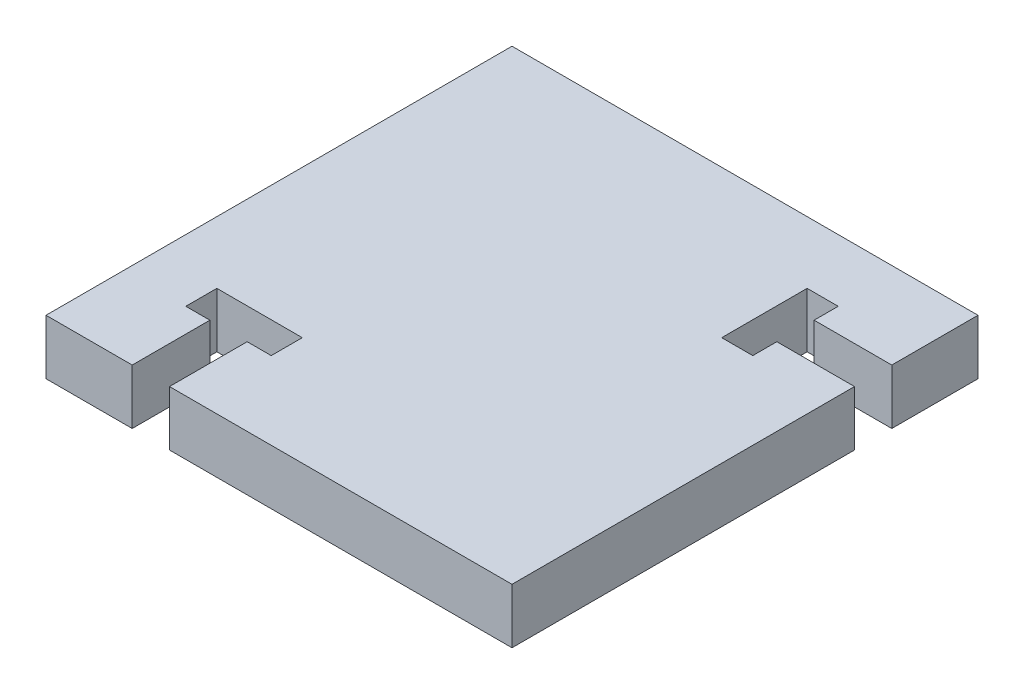
SolidWorks part; units mm, degrees
ref_plane "Front Plane" through (0, 0, 0) normal (0, 0, 1) x (1, 0, 0)
ref_plane "Top Plane" through (0, 0, 0) normal (0, 1, 0) x (1, 0, 0)
ref_plane "Right Plane" through (0, 0, 0) normal (1, 0, 0) x (0, 0, -1)
sketch "Sketch1" plane through (0, 0, 0) normal (0, 1, 0) x (1, 0, 0)
  line L0 (-31.0515, 0) -> (-31.0515, 6.35)
  line L1 (-38.1, 38.1) -> (0, 38.1)
  line L2 (-38.1, 38.1) -> (-38.1, 0)
  line L3 (-38.1, 0) -> (-31.0515, 0)
  line L4 (0, 38.1) -> (0, 31.0515)
  line L5 (-31.0515, 6.35) -> (-33.02, 6.35)
  line L6 (-33.02, 6.35) -> (-33.02, 8.89)
  line L7 (-33.02, 8.89) -> (-26.035, 8.89)
  line L8 (-26.035, 8.89) -> (-26.035, 6.35)
  line L9 (-26.035, 6.35) -> (-28.0035, 6.35)
  line L10 (-28.0035, 6.35) -> (-28.0035, 0)
  line L11 (-29.5275, 8.89) -> (-29.5275, 0) construction
  line L12 (-31.0515, 6.35) -> (-28.0035, 6.35) construction
  line L13 (-29.5275, 8.89) -> (-29.5275, 29.5275) construction
  line L14 (-29.5275, 29.5275) -> (0, 29.5275) construction
  line L15 (-38.1, 29.5275) -> (-29.5275, 29.5275) construction
  line L16 (-29.5275, 29.5275) -> (-29.5275, 38.1) construction
  line L17 (-8.89, 26.035) -> (-8.89, 33.02)
  line L18 (-6.35, 26.035) -> (-8.89, 26.035)
  line L19 (0, 28.0035) -> (-6.35, 28.0035)
  line L20 (-6.35, 28.0035) -> (-6.35, 26.035)
  line L21 (-6.35, 31.0515) -> (0, 31.0515)
  line L22 (-6.35, 33.02) -> (-6.35, 31.0515)
  line L23 (-8.89, 33.02) -> (-6.35, 33.02)
  line L24 (-29.5275, 29.5275) -> (-33.02, 8.89) construction
  line L25 (-29.5275, 29.5275) -> (-8.89, 26.035) construction
  line L26 (-28.0035, 0) -> (0, 0)
  line L27 (0, 28.0035) -> (0, 0)
  point P4 (0, 0)
  point P17 (-29.5275, 6.35)
  point P18 (-33.02, 7.62)
  dimension "D1" = 38.1
  dimension "D2" = 38.1
  dimension "D3" = 3.048
  dimension "D4" = 8.89
  dimension "D5" = 2.54
  dimension "D6" = 5.08
  dimension "D7" = 6.985
  dimension "D9" = 90
  dimension "D8" = 2
extrude "Boss-Extrude1" add sketch "Sketch1" along normal blind 4.4958
